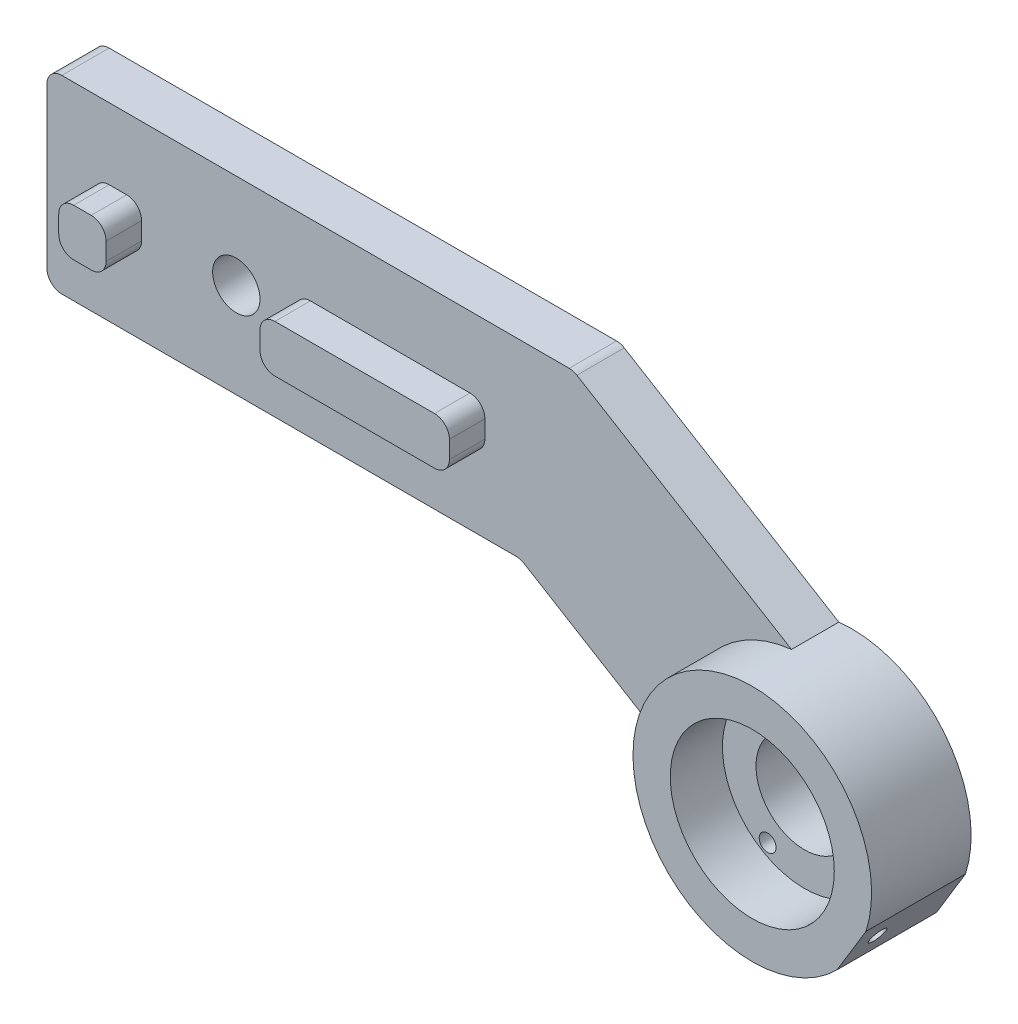
SolidWorks part; units mm, degrees
ref_plane "Front Plane" through (0, 0, 0) normal (0, 0, 1) x (1, 0, 0)
ref_plane "Top Plane" through (0, 0, 0) normal (0, 1, 0) x (1, 0, 0)
ref_plane "Right Plane" through (0, 0, 0) normal (1, 0, 0) x (0, 0, -1)
sketch "Sketch1" plane through (0, 0, 0) normal (0, 0, 1) x (1, 0, 0)
  line L0 (0, 0) -> (-25.4, 0) construction
  line L2 (-25.4, -12.7) -> (-25.4, 12.7)
  line L5 (82.7848, -10.0904) -> (69.6152, -31.8096) construction
  line L6 (38.1, -12.7) -> (61.2936, -26.7637) construction
  line L25 (45.1992, 12.7) -> (-25.4, 12.7)
  line L26 (38.1, -12.7) -> (-25.4, -12.7)
  line L27 (45.1992, 12.7) -> (74.4632, -5.0445)
  line L28 (76.2, -20.95) -> (110.4003, -41.6877) construction
  line L29 (91.4446, -25.8082) -> (87.5559, -32.2213)
  line L30 (38.1, -12.7) -> (61.2936, -26.7637)
  line L31 (81.1386, -12.8053) -> (71.2614, -29.0947) construction
  circle A0 centre (0, 0) radius 3.175
  circle A13 centre (76.2, -20.95) radius 6.5
  circle A14 centre (76.2, -20.95) radius 16 construction
  arc A15 (87.5559, -32.2213) -> (61.2936, -26.7637) centre (76.2, -20.95) cw
  arc A16 (74.4632, -5.0445) -> (91.4446, -25.8082) centre (76.2, -20.95) cw
  circle A17 centre (81.1386, -12.8053) radius 1.1303
  circle A18 centre (71.2614, -29.0947) radius 1.1303
  point P13 (89.5003, -29.0148)
  point P24 (76.2, -20.95)
  dimension "D4" = 6.35
  dimension "D7" = 32
  dimension "D8" = 25.4
  dimension "D10" = 7.5
  dimension "D5" = 20.95
  dimension "D6" = 76.2
  dimension "D9" = 13
  dimension "D14" = 2.2606
  dimension "D2" = 38.1
  dimension "D3" = 25.4
  dimension "D11" = 19.05
  dimension "D13" = 25.4
extrude "Boss-Extrude1" add sketch "Sketch1" along normal blind 6.35
sketch "Sketch5" plane through (0, 0, 6.35) normal (0, 0, 1) x (1, 0, 0)
  line L0 (-25.4, 0) -> (66.1438, 0) construction
  line L1 (-25.4, 12.7) -> (-25.4, -12.7) construction
  line L2 (74.4632, -5.0445) -> (45.1992, 12.7) construction
  line L4 (33.3375, -3.175) -> (7.9375, -3.175)
  line L5 (33.3375, -3.175) -> (33.3375, 3.175)
  line L6 (33.3375, 3.175) -> (7.9375, 3.175)
  line L7 (7.9375, -3.175) -> (7.9375, 3.175)
  line L8 (33.3375, -3.175) -> (7.9375, 3.175) construction
  line L9 (33.3375, 3.175) -> (7.9375, -3.175) construction
  line L10 (-12.7, -3.175) -> (-19.05, -3.175)
  line L11 (-12.7, -3.175) -> (-12.7, 3.175)
  line L12 (-12.7, 3.175) -> (-19.05, 3.175)
  line L13 (-19.05, -3.175) -> (-19.05, 3.175)
  line L14 (-12.7, -3.175) -> (-19.05, 3.175) construction
  line L15 (-12.7, 3.175) -> (-19.05, -3.175) construction
  point P7 (20.6375, 0)
  point P12 (-15.875, 0)
  point P17 (0, 0)
  dimension "D1" = 25.4
  dimension "D2" = 6.35
  dimension "D3" = 6.35
  dimension "D4" = 12.7
  dimension "D5" = 7.9375
extrude "Boss-Extrude3" add sketch "Sketch5" along normal blind 4.7625
sketch "Sketch4" plane through (0, 0, 6.35) normal (0, 0, 1) x (1, 0, 0)
  line L0 (91.4446, -25.8082) -> (87.5559, -32.2213)
  circle A0 centre (76.2, -20.95) radius 11
  circle A1 centre (76.2, -20.95) radius 16 construction
  arc A2 (91.4446, -25.8082) -> (87.5559, -32.2213) centre (76.2, -20.95) ccw
  dimension "D1" = 22
extrude "Boss-Extrude2" add sketch "Sketch4" along normal blind 7
sketch "Sketch2" plane through (78.3036, -47.4802, 0) normal (0.8551, -0.5185, 0) x (0, 0, -1)
  line L0 (-6.35, 21.5949) -> (-13.35, 21.5949) construction
  line L1 (-6.35, 17.8449) -> (-6.35, 25.3449) construction
  line L4 (-13.35, 17.8449) -> (-13.35, 25.3449) construction
  circle A0 centre (-9.85, 21.5949) radius 1.1303
  dimension "D1" = 2.2606
extrude "Cut-Extrude1" cut sketch "Sketch2" against normal up to next
fillet "Fillet3" radius 2 12 edges at (-25.4, -12.7, 3.175) (-25.4, 12.7, 3.175) (45.1992, 12.7, 3.175) (38.1, -12.7, 3.175) (-19.05, -3.175, 8.7312) (-12.7, -3.175, 8.7312) (7.9375, -3.175, 8.7312) (33.3375, -3.175, 8.7312) (7.9375, 3.175, 8.7312) (33.3375, 3.175, 8.7312) (-12.7, 3.175, 8.7312) (-19.05, 3.175, 8.7312)
